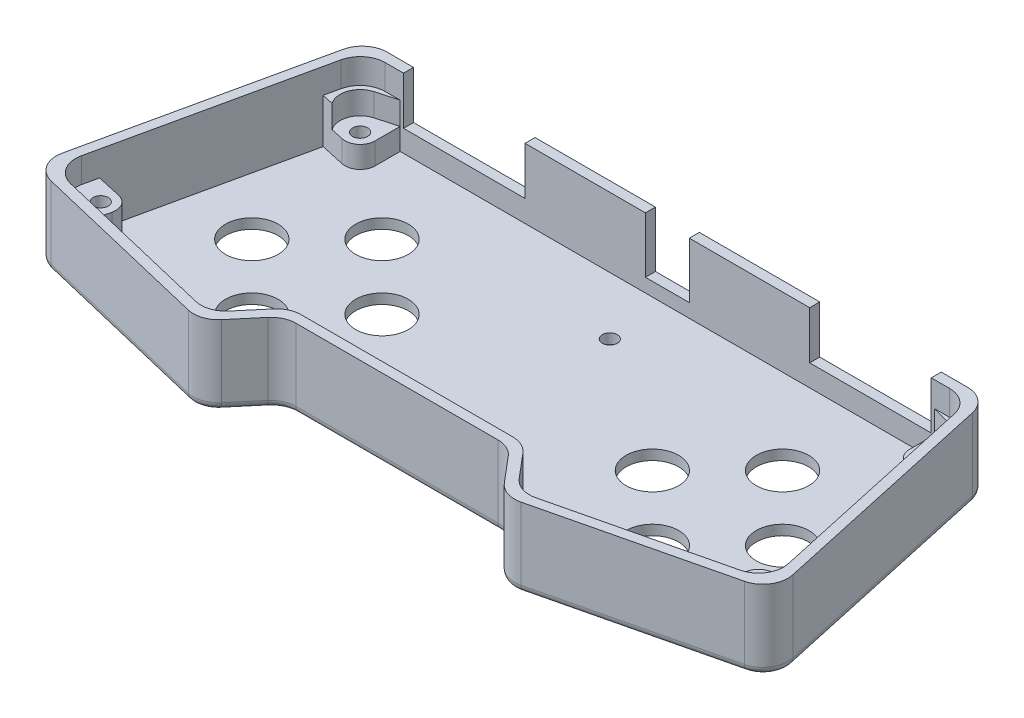
SolidWorks part; units mm, degrees
ref_plane "Front Plane" through (0, 0, 0) normal (0, 0, 1) x (1, 0, 0)
ref_plane "Top Plane" through (0, 0, 0) normal (0, 1, 0) x (1, 0, 0)
ref_plane "Right Plane" through (0, 0, 0) normal (1, 0, 0) x (0, 0, -1)
sketch "Sketch10" plane through (0, 0, 0) normal (0, 1, 0) x (1, 0, 0)
  line L0 (62, 32) -> (-62, 32)
  line L1 (-62, 32) -> (-74, -22.6992)
  line L2 (-74, -22.6992) -> (-30.236, -33.1736)
  line L3 (-30.236, -33.1736) -> (-22.5, -24)
  line L4 (-22.5, -24) -> (22.5, -24)
  line L5 (22.5, -24) -> (30.236, -33.1736)
  line L6 (30.236, -33.1736) -> (74, -22.6992)
  line L7 (74, -22.6992) -> (62, 32)
  line L8 (40, 13) -> (40, -13) construction
  line L9 (27, 0) -> (53, 0) construction
  line L10 (-40, 13) -> (-40, -13) construction
  line L11 (-53, 0) -> (-27, 0) construction
  line L12 (-27, 0) -> (27, 0) construction
  line L13 (0, 0) -> (0, 32) construction
  line L14 (0, 0) -> (0, -24) construction
  line L15 (74, -22.6992) -> (22.5, -24) construction
  line L16 (-22.5, -24) -> (-74, -22.6992) construction
  circle A0 centre (40, 13) radius 5.25
  circle A1 centre (27, 0) radius 5.25
  circle A2 centre (40, -13) radius 5.25
  circle A3 centre (53, 0) radius 5.25
  circle A4 centre (-40, 13) radius 5.25
  circle A5 centre (-53, 0) radius 5.25
  circle A6 centre (-40, -13) radius 5.25
  circle A7 centre (-27, 0) radius 5.25
  point P16 (40, 0)
  point P17 (-40, 0)
  dimension "D1" = 10.5
  dimension "D2" = 26
  dimension "D3" = 56
  dimension "D4" = 124
  dimension "D5" = 80
  dimension "D6" = 148
  dimension "D7" = 56
  dimension "D8" = 45
  dimension "D9" = 32
  dimension "D10" = 45
  dimension "D11" = 12
extrude "Boss-Extrude5" add sketch "Sketch10" along normal blind 2 separate body
sketch "Sketch11" plane through (0, 2, 0) normal (0, 1, 0) x (1, 0, 0)
  line L0 (-74, -22.6992) -> (-62, 32)
  line L1 (-62, 32) -> (62, 32)
  line L2 (62, 32) -> (74, -22.6992)
  line L3 (74, -22.6992) -> (30.236, -33.1736)
  line L4 (30.236, -33.1736) -> (22.5, -24)
  line L5 (22.5, -24) -> (-22.5, -24)
  line L6 (-22.5, -24) -> (-30.236, -33.1736)
  line L7 (-30.236, -33.1736) -> (-74, -22.6992)
  line L8 (-30.9699, -30.9414) -> (-71.6259, -21.2109)
  line L9 (-71.6259, -21.2109) -> (-60.3912, 30)
  line L10 (-60.3912, 30) -> (60.3912, 30)
  line L11 (60.3912, 30) -> (71.6259, -21.2109)
  line L12 (71.6259, -21.2109) -> (30.9699, -30.9414)
  line L13 (30.9699, -30.9414) -> (23.4296, -22)
  line L14 (23.4296, -22) -> (-23.4296, -22)
  line L15 (-23.4296, -22) -> (-30.9699, -30.9414)
  dimension "D1" = 2
extrude "Boss-Extrude7" add sketch "Sketch11" along direction (0, -1, 0) on the side of the normal offset from surface (13.875 mm away) 15.875 up to face at (-40, 0, 18.25)
fillet "Fillet4" radius 5 16 edges at (62, 7.9375, -32) (74, 7.9375, 22.6992) (30.236, 7.9375, 33.1736) (22.5, 7.9375, 24) (-22.5, 7.9375, 24) (-30.236, 7.9375, 33.1736) (-62, 7.9375, -32) (-74, 7.9375, 22.6992) (71.6259, 8.9375, 21.2109) (60.3912, 8.9375, -30) (30.9699, 8.9375, 30.9414) (23.4296, 8.9375, 22) (-23.4296, 8.9375, 22) (-30.9699, 8.9375, 30.9414) (-71.6259, 8.9375, 21.2109) (-60.3912, 8.9375, -30)
fillet "Fillet5" radius 1.5 16 edges at (30.509, 0, 32.3431) (26.1233, 0, 28.2966) (22.2835, 0, 24.4659) (0, 0, 24) (-22.2835, 0, 24.4659) (-26.1233, 0, 28.2966) (-30.509, 0, 32.3431) (-51.2316, 0, 28.1485) (-72.3012, 0, 21.6342) (-67.9053, 0, -5.0822) (-61.1119, 0, -30.896) (0, 0, -32) (61.1119, 0, -30.896) (67.9053, 0, -5.0822) (72.3012, 0, 21.6342) (51.2316, 0, 28.1485)
sketch "Sketch12" plane through (0, 2, 0) normal (0, 1, 0) x (1, 0, 0)
  line L0 (-61.8959, 23.1411) -> (-57.0121, 22.0697)
  line L1 (-61.2531, 26.0714) -> (-70.5746, -16.4188) construction
  line L2 (-53.3692, 25) -> (-53.3692, 30)
  line L3 (56.3692, 30) -> (-56.3692, 30) construction
  line L4 (-53.3692, 30) -> (-56.3692, 30)
  line L5 (-61.2531, 26.0714) -> (-61.8959, 23.1411)
  line L6 (-70.5746, -16.4188) -> (-69.9318, -13.4885)
  line L7 (-69.9318, -13.4885) -> (-65.0479, -14.5599)
  line L8 (-62.7732, -18.1885) -> (-63.937, -23.0512)
  line L9 (-66.8546, -22.3529) -> (-33.9684, -30.2238) construction
  line L10 (-63.937, -23.0512) -> (-66.8546, -22.3529)
  line L11 (0, 0) -> (0, 17.9434) construction
  line L12 (63.937, -23.0512) -> (66.8546, -22.3529)
  line L13 (62.7732, -18.1885) -> (63.937, -23.0512)
  line L14 (69.9318, -13.4885) -> (65.0479, -14.5599)
  line L15 (70.5746, -16.4188) -> (69.9318, -13.4885)
  line L16 (61.2531, 26.0714) -> (61.8959, 23.1411)
  line L17 (53.3692, 30) -> (56.3692, 30)
  line L18 (53.3692, 25) -> (53.3692, 30)
  line L19 (61.8959, 23.1411) -> (57.0121, 22.0697)
  arc A0 (-57.0121, 22.0697) -> (-53.3692, 25) centre (-56.3692, 25) ccw
  arc A1 (-56.3692, 30) -> (-61.2531, 26.0714) centre (-56.3692, 25) ccw
  arc A2 (-65.0479, -14.5599) -> (-62.7732, -18.1885) centre (-65.6908, -17.4902) cw
  arc A3 (-66.8546, -22.3529) -> (-70.5746, -16.4188) centre (-65.6908, -17.4902) cw
  circle A4 centre (-56.3692, 25) radius 1.5
  circle A5 centre (-65.6908, -17.4902) radius 1.5
  circle A6 centre (65.6908, -17.4902) radius 1.5
  circle A7 centre (56.3692, 25) radius 1.5
  arc A8 (66.8546, -22.3529) -> (70.5746, -16.4188) centre (65.6908, -17.4902) ccw
  arc A9 (65.0479, -14.5599) -> (62.7732, -18.1885) centre (65.6908, -17.4902) ccw
  arc A10 (56.3692, 30) -> (61.2531, 26.0714) centre (56.3692, 25) cw
  arc A11 (57.0121, 22.0697) -> (53.3692, 25) centre (56.3692, 25) cw
  dimension "D1" = 3
  dimension "D2" = 1.5
extrude "Boss-Extrude8" add sketch "Sketch12" along normal offset from surface (8.875 mm away) 5 up to face at (0, 15.875, 10.9337)
sketch "Sketch14" plane through (0, 0, -30) normal (0, 0, 1) x (1, 0, 0)
  line L0 (-56.3692, 15.875) -> (56.3692, 15.875) construction
  line L1 (-52.7009, 15.875) -> (-28.427, 15.875)
  line L2 (-52.7009, 15.875) -> (-52.7009, 6.3348)
  line L3 (-52.7009, 6.3348) -> (-28.427, 6.3348)
  line L4 (-28.427, 15.875) -> (-28.427, 6.3348)
  line L5 (0, 0) -> (0, 15.875) construction
  line L6 (28.427, 15.875) -> (28.427, 6.3348)
  line L7 (52.7009, 6.3348) -> (28.427, 6.3348)
  line L8 (52.7009, 15.875) -> (52.7009, 6.3348)
  line L9 (52.7009, 15.875) -> (28.427, 15.875)
  line L11 (-4.3796, 15.875) -> (4.3796, 15.875)
  line L12 (-4.3796, 15.875) -> (-4.3796, 4.7297)
  line L13 (-4.3796, 4.7297) -> (4.3796, 4.7297)
  line L14 (4.3796, 15.875) -> (4.3796, 4.7297)
extrude "Cut-Extrude2" cut sketch "Sketch14" against normal through all
sketch "Sketch13" plane through (0, 10.875, 0) normal (0, 1, 0) x (1, 0, 0)
  line L0 (-57.4531, 28.8503) -> (-53.3692, 30)
  line L1 (-53.3692, 30) -> (-52.4618, 25.8555)
  line L2 (57.4531, 28.8503) -> (53.3692, 30)
  line L3 (53.3692, 30) -> (52.4618, 25.8555)
  arc A0 (-57.4531, 28.8503) -> (-52.4618, 25.8555) centre (-56.3692, 25) ccw
  arc A1 (52.4618, 25.8555) -> (57.4531, 28.8503) centre (56.3692, 25) ccw
  dimension "D1" = 8
extrude "Cut-Extrude1" cut sketch "Sketch13" against normal up to surface (4.5402 mm away) up to face at (-40.5639, 6.3348, -31)
sketch "Sketch15" plane through (0, 0, 0) normal (0, -1, 0) x (1, 0, 0)
  line L0 (0, -18.5) -> (0, -30.5) construction
  line L1 (-57.978, -30.5) -> (57.978, -30.5) construction
  circle A0 centre (0, -18.5) radius 1.5
  dimension "D2" = 3
  dimension "D1" = 12
extrude "Cut-Extrude3" cut sketch "Sketch15" against normal through all contours A0
